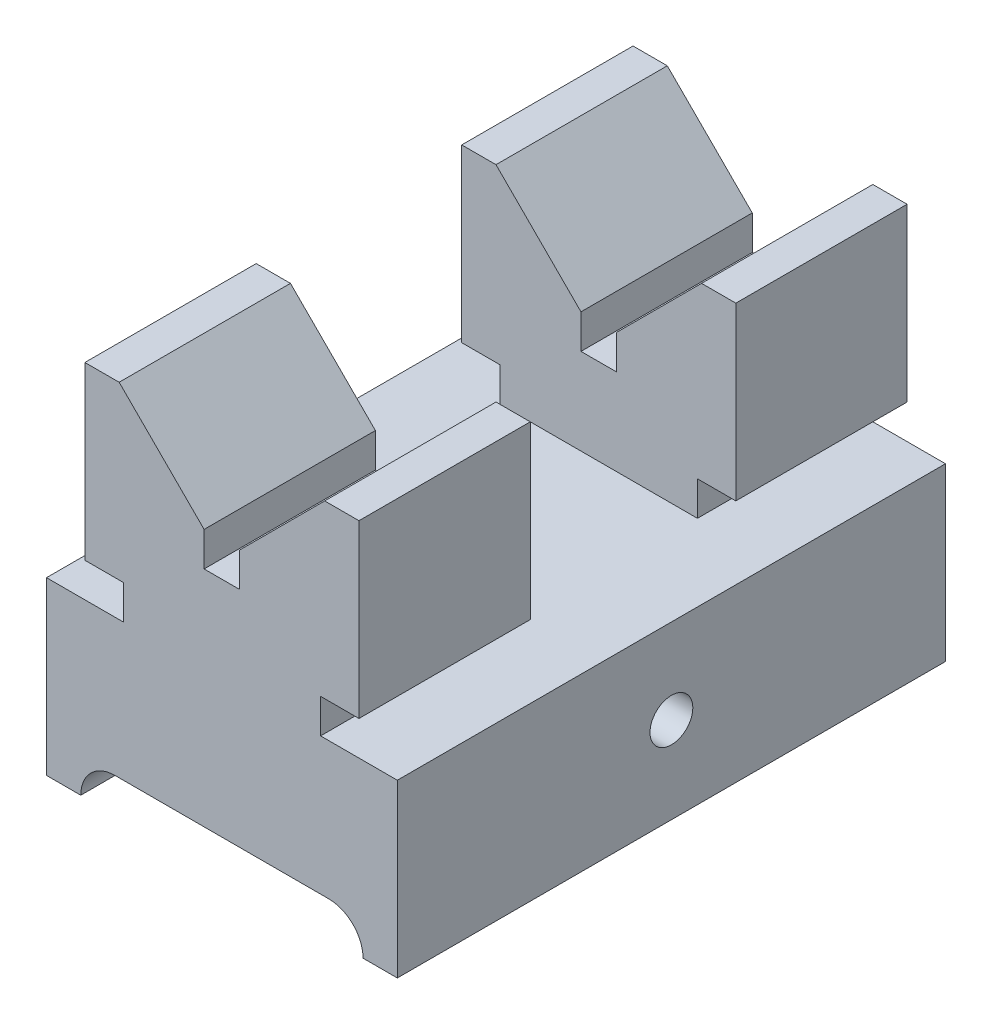
SolidWorks part; units mm, degrees
ref_plane "Front Plane" through (0, 0, 0) normal (0, 0, 1) x (1, 0, 0)
ref_plane "Top Plane" through (0, 0, 0) normal (0, 1, 0) x (1, 0, 0)
ref_plane "Right Plane" through (0, 0, 0) normal (1, 0, 0) x (0, 0, -1)
sketch "Sketch1" plane through (0, 0, 0) normal (0, 0, 1) x (1, 0, 0)
  line L0 (-58.674, 0) -> (-58.674, 6.35)
  line L1 (-65.024, 31.75) -> (0, 31.75)
  line L2 (-65.024, 31.75) -> (-65.024, 0)
  line L3 (-65.024, 0) -> (-58.674, 0)
  line L4 (0, 31.75) -> (0, 0)
  line L5 (-58.674, 6.35) -> (-6.35, 6.35)
  line L6 (-6.35, 6.35) -> (-6.35, 0)
  line L7 (-6.35, 0) -> (0, 0)
  dimension "D1" = 65.024
  dimension "D2" = 31.75
  dimension "D3" = 6.35
  dimension "D4" = 6.35
extrude "Boss-Extrude1" add sketch "Sketch1" along normal blind 101.6
fillet "Fillet1" radius 6.35 1 edges at (-6.35, 6.35, 50.8)
fillet "Fillet2" radius 6.35 1 edges at (-58.674, 6.35, 50.8)
hole_wizard "3/8-16 Tapped Hole3" positions "Sketch7" profile "Sketch8" tap size "3/8-16" standard "ANSI Inch"
sketch "Sketch7" plane through (0, 0, 0) normal (0, 0, -1) x (-1, 0, 0)
  line L0 (0, 0) -> (0, 31.75) construction
  line L1 (52.324, 6.35) -> (12.7, 6.35) construction
  point P0 (31.75, 22.352)
  dimension "D1" = 31.75
  dimension "D2" = 16.002
sketch "Sketch8" plane through (-31.75, 22.352, 0) normal (1, 0, 0) x (0, 1, 0)
  line L0 (0, 0) -> (0, 18.3867)
  line L1 (0, 18.3867) -> (3.9687, 16.002)
  line L2 (3.9687, 16.002) -> (3.9687, 0)
  line L5 (3.9687, 0) -> (0, 0)
  line L10 (0, 18.3867) -> (-3.9688, 16.002) construction
  line L11 (0, -6.35) -> (0, 107.95) construction
  dimension "Tap Drill Dia." = 7.9375
  dimension "Tap Drill Depth" = 16.002
  dimension "Drill Angle" = 118
cosmetic thread "Hole Thread3" parameters "D1"=19.05, "D2"=9.525
hole_wizard "3/8-16 Tapped Hole4" positions "Sketch9" profile "Sketch11" tap size "3/8-16" standard "ANSI Inch" end condition through all
sketch "Sketch9" plane through (0, 0, 0) normal (1, 0, 0) x (0, 0, -1)
  line L0 (0, 0) -> (0, 31.75) construction
  line L1 (-101.6, 0) -> (0, 0) construction
  point P0 (-50.8, 16.002)
  dimension "D1" = 50.8
  dimension "D2" = 16.002
sketch "Sketch11" plane through (0, 16.002, 50.8) normal (0, 1, 0) x (0, 0, -1)
  line L0 (0, 0) -> (0, 65.024)
  line L1 (0, 65.024) -> (3.9687, 65.024)
  line L2 (3.9687, 65.024) -> (3.9687, 0)
  line L5 (3.9687, 0) -> (0, 0)
  line L11 (0, -6.35) -> (0, 107.95) construction
  dimension "Thru Tap Drill Dia." = 7.9375
  dimension "Thru Tap Drill Depth" = 65.024
cosmetic thread "Hole Thread4" parameters "D2"=9.525
sketch "Sketch13" plane through (0, 0, 0) normal (0, 0, 1) x (1, 0, 0)
  line L0 (-14.224, 31.75) -> (-14.224, 38.1)
  line L1 (0, 31.75) -> (-65.024, 31.75) construction
  line L2 (-14.224, 38.1) -> (-7.112, 38.1)
  line L3 (-7.112, 38.1) -> (-7.112, 69.85)
  line L4 (-7.112, 69.85) -> (-13.462, 69.85)
  line L5 (-13.462, 69.85) -> (-29.21, 54.102)
  line L6 (-29.21, 54.102) -> (-29.21, 47.752)
  line L7 (-29.21, 47.752) -> (-35.814, 47.752)
  line L8 (-35.814, 47.752) -> (-35.814, 54.102)
  line L9 (-35.814, 54.102) -> (-51.562, 69.85)
  line L10 (-51.562, 69.85) -> (-57.912, 69.85)
  line L11 (-57.912, 69.85) -> (-57.912, 38.1)
  line L12 (-57.912, 38.1) -> (-50.8, 38.1)
  line L13 (-50.8, 38.1) -> (-50.8, 31.75)
  line L14 (-14.224, 31.75) -> (-50.8, 31.75)
  line L15 (0, 0) -> (0, 31.75) construction
  line L16 (-65.024, 0) -> (-58.674, 0) construction
  point P20 (-44.4672, 49.8938)
  point P21 (-48.9781, 55.4034)
  point P22 (0, 0)
  point P23 (-48.0623, 54.918)
  point P24 (-21.3173, 37.1108)
  point P25 (-21.2805, 36.5685)
  point P26 (-14.4768, 36.3963)
  point P27 (-30.4172, 49.1164)
  point P28 (-27.3692, 59.6663)
  point P29 (-33.1461, 47.752)
  point P30 (-38.8122, 47.752)
  point P31 (0, 0)
  point P32 (-14.224, 34.925)
  point P33 (-27.1174, 58.8985)
  point P34 (-26.5897, 54.5587)
  point P35 (-48.7119, 69.85)
  point P36 (-23.2713, 54.937)
  point P37 (-57.7539, 38.1)
  point P38 (-7.498, 38.1)
  point P39 (-25.8413, 54.8963)
  point P40 (-7.6131, 38.1)
  point P41 (-51.8455, 69.85)
  dimension "D1" = 50.8
  dimension "D2" = 47.752
  dimension "D3" = 69.85
  dimension "D4" = 38.1
  dimension "D5" = 14.224
  dimension "D6" = 90
  dimension "D7" = 22.098
  dimension "D8" = 28.702
  dimension "D9" = 44.45
extrude "Boss-Extrude2" add sketch "Sketch13" along normal blind 31.75 contours L14 L13 L12 L11 L10 L9 L8 L7 L6 L5 L4 L3 L2 L0
ref_plane "Plane1" through (-65.024, 31.75, 0) normal (0, 0, -1) x (-1, 0, 0)
sketch "Sketch15" plane through (0, 31.75, 0) normal (0, 1, 0) x (1, 0, 0)
  line L0 (-65.024, -50.8) -> (0, -50.8) construction
  line L2 (0, -101.6) -> (0, 0) construction
  line L3 (-65.024, -101.6) -> (-65.024, 0) construction
  point P0 (-65.024, -50.8)
  point P3 (-32.512, -50.8)
ref_plane "Plane2" through (0, 0, 50.8) normal (0, 0, 1) x (1, 0, 0)
mirror "Mirror1" about plane through (0, 0, 50.8) normal (0, 0, 1) of "Boss-Extrude2"
